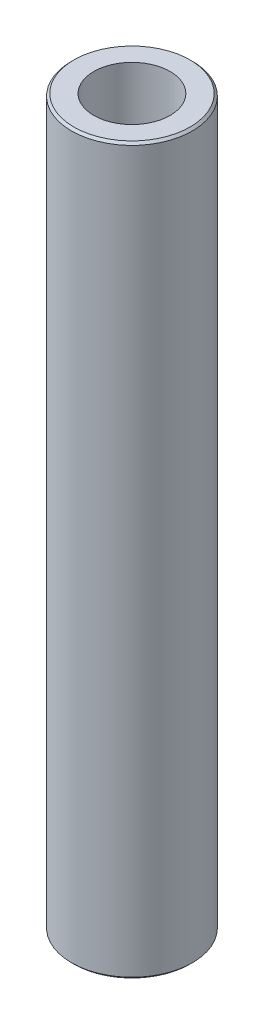
SolidWorks part; units mm, degrees
ref_plane "Front Plane" through (0, 0, 0) normal (0, 0, 1) x (1, 0, 0)
ref_plane "Top Plane" through (0, 0, 0) normal (0, 1, 0) x (1, 0, 0)
ref_plane "Right Plane" through (0, 0, 0) normal (1, 0, 0) x (0, 0, -1)
sketch "Sketch1" plane through (0, 0, 0) normal (0, 1, 0) x (1, 0, 0)
  circle A0 centre (0, 0) radius 50
  dimension "SHAFT_OD" = 100
extrude "Boss-Extrude1" add sketch "Sketch1" along normal blind 600
sketch "Sketch2" plane through (0, 0, 0) normal (0, 1, 0) x (1, 0, 0)
  circle A0 centre (0, 0) radius 31.5602
  dimension "BORE_D" = 63.1204
extrude "Cut-Extrude1" cut sketch "Sketch2" along normal through all
chamfer "Chamfer1" distance 1.8865 angle 45 2 edges at (0, 600, 50) (0, 0, 50)
